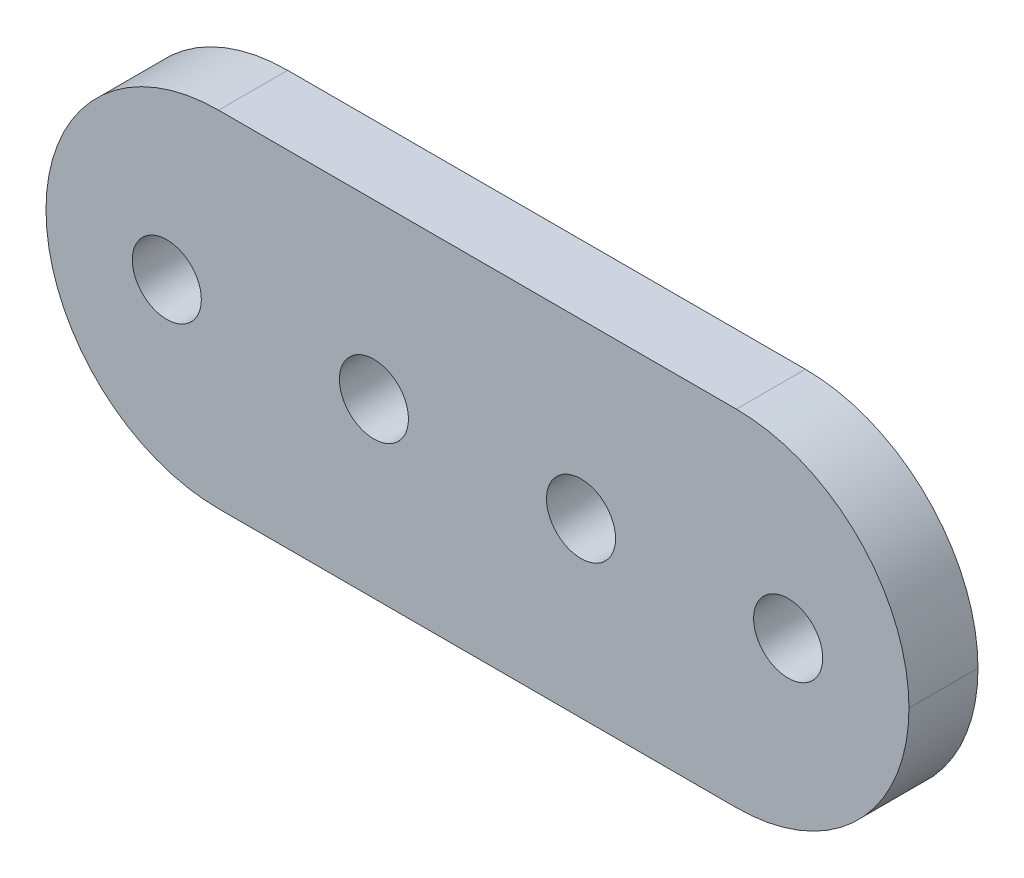
SolidWorks part; units mm, degrees
ref_plane "前视基准面" through (0, 0, 0) normal (0, 0, 1) x (1, 0, 0)
ref_plane "上视基准面" through (0, 0, 0) normal (0, 1, 0) x (1, 0, 0)
ref_plane "右视基准面" through (0, 0, 0) normal (1, 0, 0) x (0, 0, -1)
sketch "草图1" plane through (0, 0, 0) normal (0, 0, 1) x (1, 0, 0)
  line L0 (0, -10) -> (50, -10) construction
  line L1 (0, 0) -> (50, 0)
  line L2 (0, 0) -> (0, -20)
  line L3 (0, -20) -> (50, -20)
  line L4 (50, 0) -> (50, -20)
  line L5 (25, 0) -> (25, -20) construction
  circle A0 centre (7, -10) radius 2
  circle A1 centre (19, -10) radius 2
  circle A2 centre (31, -10) radius 2
  circle A3 centre (43, -10) radius 2
  dimension "D3" = 4
  dimension "D4" = 4
  dimension "D5" = 4
  dimension "D6" = 4
  dimension "D7" = 7
  dimension "D8" = 6
  dimension "D9" = 6
  dimension "D10" = 7
  dimension "D1" = 50
  dimension "D2" = 20
extrude "凸台-拉伸1" add sketch "草图1" along normal blind 4
fillet "圆角1" radius 10 4 edges at (50, 0, 2) (50, -20, 2) (0, -20, 2) (0, 0, 2)
sketch "草图2" plane through (0, 0, 0) normal (0, 0, -1) x (-1, 0, 0)
  line L0 (-25, -20) -> (-25, 0) construction
  line L1 (-10, -20) -> (-40, -20) construction
  line L2 (-40, 0) -> (-10, 0) construction
